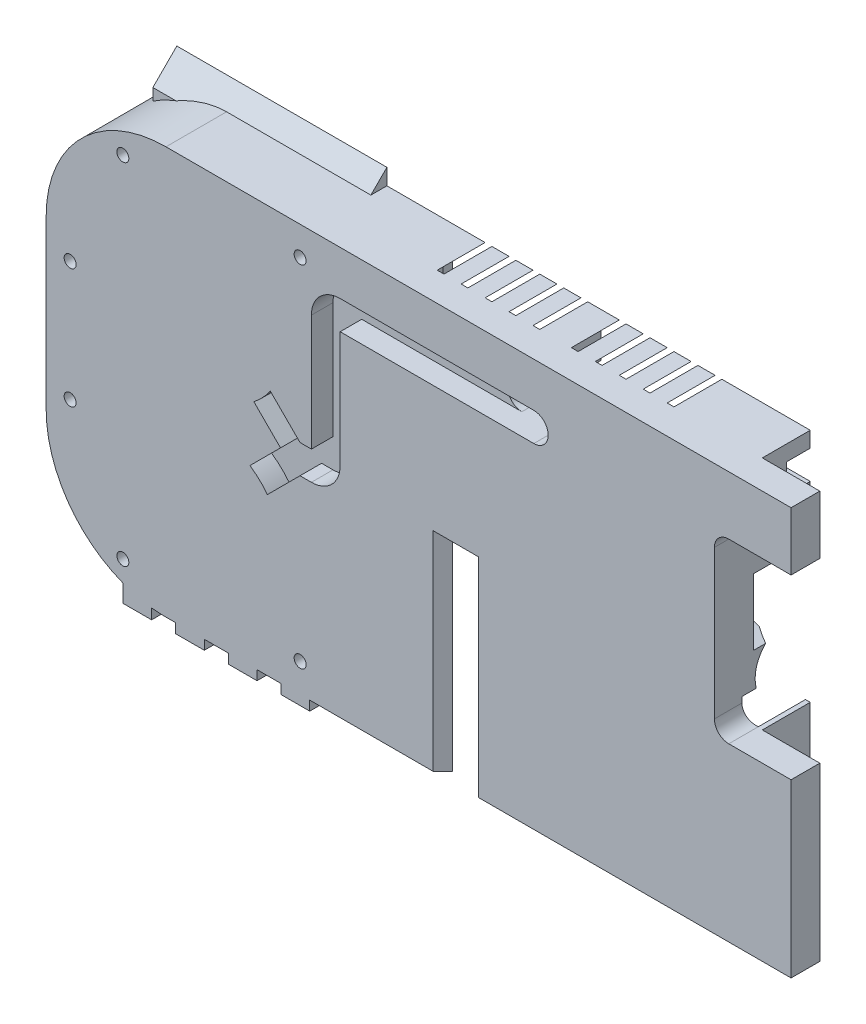
SolidWorks part; units mm, degrees
ref_plane "Front Plane" through (0, 0, 0) normal (0, 0, 1) x (1, 0, 0)
ref_plane "Top Plane" through (0, 0, 0) normal (0, 1, 0) x (1, 0, 0)
ref_plane "Right Plane" through (0, 0, 0) normal (1, 0, 0) x (0, 0, -1)
sketch "mech-front" plane through (0, 0, 0) normal (0, 0, 1) x (1, 0, 0)
  line L0 (-90.64, 57.83) -> (-90.64, 97.83) construction
  line L4 (74.3789, 74.83) -> (74.3789, 82.0953) construction
  line L5 (41.8228, 3) -> (41.8228, 36) construction
  line L6 (-40.1772, 3) -> (-40.1772, 36) construction
  line L7 (-40.64, 97.83) -> (-40.64, 57.83) construction
  line L12 (-85.7883, 97.83) -> (-90.64, 97.83)
  line L13 (-90.64, 97.83) -> (-90.64, 57.83)
  line L14 (-90.64, 57.83) -> (-85.7883, 57.83)
  line L15 (-45.4916, 57.83) -> (-40.64, 57.83)
  line L16 (-40.64, 57.83) -> (-40.64, 97.83)
  line L17 (-40.64, 97.83) -> (-45.4916, 97.83)
  line L20 (39.9162, 72.83) -> (70.9162, 72.83)
  line L21 (74.3789, 74.83) -> (74.3789, 105.83)
  line L22 (70.9162, 107.83) -> (39.9162, 107.83)
  line L23 (37.9162, 105.83) -> (37.9162, 74.83)
  line L26 (-47.1772, 0) -> (-47.1772, 36)
  line L27 (54.8228, 36) -> (54.8228, 0)
  line L28 (54.8228, 36) -> (41.8228, 36)
  line L30 (-40.1772, 36) -> (41.8228, 36)
  line L31 (-40.1772, 36) -> (-47.1772, 36)
  line L34 (-24.2711, 85.48) -> (56.8789, 85.48)
  line L35 (56.8789, 95.18) -> (-24.2711, 95.18)
  line L38 (-30.2119, 75.9) -> (-33.1772, 75.9)
  line L39 (-40.1772, 68.9) -> (-40.1772, 36)
  line L42 (32.71, 75.9) -> (26.935, 75.9)
  line L43 (41.8228, 68.9) -> (41.8228, 36)
  line L46 (22.035, 75.9) -> (22.035, 88.1)
  line L47 (-23.965, 88.1) -> (-23.965, 75.9)
  line L78 (-30.2119, 75.9) -> (26.935, 75.9)
  line L79 (22.035, 88.1) -> (-23.965, 88.1)
  arc A1 (-24.2711, 95.18) -> (-24.2711, 85.48) centre (-24.2711, 90.33) ccw
  arc A7 (41.8228, 68.9) -> (32.71, 75.9) centre (34.8305, 69.2289) ccw
  arc A8 (-24.2711, 95.18) -> (-24.2711, 85.48) centre (-24.2711, 90.33) ccw construction
  arc A12 (70.9162, 72.83) -> (74.3789, 74.83) centre (72.6234, 73.8718) ccw
  arc A13 (74.3789, 105.83) -> (70.9162, 107.83) centre (72.6234, 106.7882) ccw
  arc A14 (39.9162, 107.83) -> (37.9162, 105.83) centre (39.9162, 105.83) ccw
  arc A15 (37.9162, 74.83) -> (39.9162, 72.83) centre (39.9162, 74.83) ccw
  circle A18 centre (78.6862, 90.2827) radius 1.65
  circle A19 centre (28.1462, 90.2827) radius 1.65
  arc A21 (-45.4916, 97.83) -> (-85.7883, 97.83) centre (-65.64, 96.74) ccw
  arc A23 (-85.7883, 57.83) -> (-45.4916, 57.83) centre (-65.64, 58.92) ccw
  arc A28 (-33.1772, 75.9) -> (-40.1772, 68.9) centre (-33.1772, 68.9) ccw
  dimension "D3" = 7
sketch "Sketch2" plane through (0, 0, 0) normal (0, 0, 1) x (1, 0, 0)
  line L0 (-75.6342, 36) -> (-73.6342, 36)
  line L1 (54.8228, 108.83) -> (54.8228, 121)
  line L2 (54.8228, 121) -> (-75.6342, 121)
  line L3 (-100.6342, 96) -> (-100.6342, 61)
  line L4 (54.8228, 36) -> (54.8228, 66.789)
  line L5 (-45.6342, 31.51) -> (-45.6342, 125.2885) construction
  line L6 (54.8228, 66.789) -> (54.8228, 71.83)
  line L7 (-67.6342, 36) -> (-62.6342, 36)
  line L8 (-45.6342, 36) -> (54.8228, 36)
  line L9 (-45.6342, 36) -> (-45.6342, 34)
  line L10 (-45.6342, 34) -> (-51.6342, 34)
  line L11 (-51.6342, 36) -> (-51.6342, 34)
  line L13 (-56.6342, 36) -> (-56.6342, 34)
  line L14 (-56.6342, 34) -> (-62.6342, 34)
  line L15 (-62.6342, 36) -> (-62.6342, 34)
  line L16 (-56.6342, 36) -> (-51.6342, 36)
  line L17 (-67.6342, 36) -> (-67.6342, 34)
  line L18 (-67.6342, 34) -> (-73.6342, 34)
  line L19 (-73.6342, 36) -> (-73.6342, 34)
  line L20 (-40.1772, 36) -> (-47.1772, 36) construction
  line L22 (-78.6342, 36.1807) -> (-78.6342, 34)
  line L23 (-78.6342, 34) -> (-84.6342, 34)
  line L28 (38.8228, 105.83) -> (38.8228, 74.83)
  line L29 (41.8228, 71.83) -> (54.8228, 71.83)
  line L30 (-84.6342, 37.6762) -> (-84.6342, 34)
  line L31 (54.8228, 108.83) -> (41.8228, 108.83)
  arc A0 (-100.6342, 61) -> (-84.6342, 37.6762) centre (-75.6342, 61) ccw
  arc A1 (-75.6342, 121) -> (-100.6342, 96) centre (-75.6342, 96) ccw
  arc A2 (-78.6342, 36.1807) -> (-75.6342, 36) centre (-75.6342, 61) ccw
  arc A3 (38.8228, 105.83) -> (41.8228, 108.83) centre (41.8228, 105.83) cw
  arc A4 (41.8228, 71.83) -> (38.8228, 74.83) centre (41.8228, 74.83) cw
  point P10 (-100.6342, 36)
  point P13 (-100.6342, 121)
  dimension "D3" = 25
  dimension "D4" = 25
  dimension "D17" = 3
  dimension "D18" = 3
  dimension "D2" = 85
  dimension "D5" = 55
  dimension "D6" = 5
  dimension "D7" = 5
  dimension "D8" = 5
  dimension "D9" = 6
  dimension "D10" = 6
  dimension "D11" = 6
  dimension "D12" = 6
  dimension "D13" = 2
  dimension "D14" = 12.17
  dimension "D15" = 37
  dimension "D16" = 16
  dimension "D19" = 155.457
extrude "body" add sketch "Sketch2" against normal blind 16
sketch "Sketch24" plane through (0, 0, -16) normal (0, 0, -1) x (-1, 0, 0)
  line L0 (-41.8228, 108.83) -> (-54.8228, 108.83) construction
  line L1 (-54.8228, 121) -> (-42.8228, 121)
  line L2 (-54.8228, 121) -> (-54.8228, 108.83)
  line L3 (-54.8228, 108.83) -> (-42.8228, 108.83)
  line L4 (-42.8228, 121) -> (-42.8228, 108.83)
  line L5 (75.6342, 36) -> (73.6342, 36) construction
  line L6 (-54.8228, 71.83) -> (-42.8228, 71.83)
  line L7 (-54.8228, 71.83) -> (-54.8228, 36)
  line L8 (-54.8228, 36) -> (-42.8228, 36)
  line L9 (-42.8228, 71.83) -> (-42.8228, 36)
  dimension "D1" = 12
  dimension "D2" = 12
extrude "handle mate" cut sketch "Sketch24" against normal blind 10
sketch "Sketch17" plane through (0, 0, -16) normal (0, 0, -1) x (-1, 0, 0)
  line L0 (-42.8228, 121) -> (75.6342, 121) construction
  line L1 (45.5249, 121) -> (75.6342, 121)
  line L2 (45.5249, 121) -> (45.5249, 125.3507)
  line L3 (45.5249, 125.3507) -> (89.3694, 125.3507)
  line L4 (89.3694, 121) -> (89.3694, 125.3507)
  line L5 (89.3694, 121) -> (89.3694, 116.8889)
  arc A0 (100.6342, 96) -> (75.6342, 121) centre (75.6342, 96) ccw construction
  arc A1 (89.3694, 116.8889) -> (75.6342, 121) centre (75.6342, 96) ccw
extrude "aim" add sketch "Sketch17" against normal blind 5
chamfer "aim chamf" distance 6 angle 45 1 edges at (-67.4471, 125.3507, -11)
sketch "Sketch4" plane through (0, 36, 0) normal (0, -1, 0) x (1, 0, 0)
  line L0 (-40.1772, -16) -> (-40.1772, -6.393)
  line L1 (41.8228, -6.8) -> (41.8228, -25.2) construction
  line L3 (-40.1772, -6.393) -> (-30.1772, -4.8597)
  line L4 (-30.1772, -4.8597) -> (-30.1772, -5.2667)
  line L5 (-30.1772, -5.2667) -> (-28.6772, -5.0367)
  line L6 (-28.6772, -5.0367) -> (-28.6772, -4.6297)
  line L7 (-28.6772, -4.6297) -> (-25.1772, -4.093)
  line L8 (-25.1772, -4.093) -> (-25.1772, -2)
  line L9 (-25.1772, -2) -> (-11.7772, -2)
  line L10 (-11.7772, -2) -> (-11.7772, -3)
  line L11 (-11.7772, -3) -> (-10.1772, -3)
  line L12 (-10.1772, -3) -> (-10.1772, -2)
  line L13 (-10.1772, -2) -> (11.8228, -2)
  line L14 (11.8228, -2) -> (11.8228, -3)
  line L15 (11.8228, -3) -> (13.4228, -3)
  line L16 (13.4228, -3) -> (13.4228, -2)
  line L17 (13.4228, -2) -> (24.32, -2)
  line L18 (24.32, -2) -> (24.32, -6.5)
  line L19 (24.32, -6.5) -> (28.82, -6.5)
  line L20 (28.82, -6.5) -> (28.82, -4.1992)
  line L21 (28.82, -4.1992) -> (30.2228, -4.4143)
  line L22 (30.2228, -4.4143) -> (30.2228, -5.0213)
  line L23 (30.2228, -5.0213) -> (31.8228, -5.2667)
  line L24 (31.8228, -5.2667) -> (31.8228, -4.6597)
  line L25 (31.8228, -4.6597) -> (41.8228, -6.193)
  line L26 (41.8228, -6.193) -> (41.8228, -16)
  line L28 (-75.6342, -16) -> (-73.6342, -16) construction
  line L29 (-40.1772, -16) -> (41.8228, -16)
extrude "clip body clearance" cut sketch "Sketch4" against normal blind 40
sketch "Sketch5" plane through (0, 76, 0) normal (0, -1, 0) x (1, 0, 0)
  line L9 (-11.7772, -2) -> (-25.1772, -2) construction
  line L10 (-11.7772, -3) -> (-11.7772, -2) construction
  line L11 (-10.1772, -3) -> (-11.7772, -3) construction
  line L12 (-10.1772, -2) -> (-10.1772, -3) construction
  line L13 (11.8228, -2) -> (-10.1772, -2) construction
  line L14 (11.8228, -3) -> (11.8228, -2) construction
  line L15 (13.4228, -2) -> (13.4228, -3) construction
  line L16 (13.4228, -3) -> (11.8228, -3) construction
  line L17 (24.32, -2) -> (13.4228, -2) construction
  line L18 (-11.7772, -2) -> (-25.1772, -2)
  line L19 (-11.7772, -3) -> (-11.7772, -2)
  line L21 (-10.1772, -3) -> (-11.7772, -3)
  line L22 (-10.1772, -2) -> (-10.1772, -3)
  line L23 (11.8228, -2) -> (-10.1772, -2)
  line L24 (11.8228, -3) -> (11.8228, -2)
  line L25 (13.4228, -2) -> (13.4228, -3)
  line L26 (13.4228, -3) -> (11.8228, -3)
  line L27 (24.32, -2) -> (13.4228, -2)
  line L28 (-25.1772, -2) -> (-25.1772, -16)
  line L29 (-40.1772, -16) -> (38.8228, -16) construction
  line L30 (24.32, -2) -> (24.32, -16)
  line L31 (24.32, -16) -> (-25.1772, -16)
extrude "clip head clearance" cut sketch "Sketch5" against normal blind 13
sketch "Sketch30" plane through (0, 0, 0) normal (0, 0, 1) x (1, 0, 0)
  line L1 (-45.6342, 36) -> (54.8228, 36) construction
  line L2 (-12.3772, 36) -> (-17.8772, 36)
  line L3 (-12.3772, 36) -> (-12.3772, 77.5)
  line L4 (-12.3772, 77.5) -> (-17.8772, 77.5)
  line L8 (-17.8772, 36) -> (-17.8772, 77.5)
  line L9 (-12.3772, 19.5) -> (-12.3772, 36) construction
  line L10 (-17.8772, 19.5) -> (-12.3772, 19.5) construction
  line L11 (-17.8772, 36) -> (-17.8772, 19.5) construction
  point P8 (-15.1272, 19.5)
  dimension "D1" = 58
extrude "clip window" cut sketch "Sketch30" against normal up to next
chamfer "clip window chamf" distance 2 angle 45 3 edges at (-17.8772, 56.75, 0) (-15.1272, 77.5, 0) (-12.3772, 56.75, 0)
hole_wizard "clip screw M3" positions "Sketch21" profile "Sketch20" tap size "M3" standard "DIN"
sketch "Sketch21" plane through (0, 36, 0) normal (0, -1, 0) x (-1, 0, 0)
  point P0 (-51.8228, 3)
  point P2 (42.1772, 3)
sketch "Sketch20" plane through (51.8228, 36, -3) normal (1, 0, 0) x (0, 0, -1)
  line L0 (0, 0) -> (0, 16.7511)
  line L1 (0, 16.7511) -> (1.25, 16)
  line L2 (1.25, 16) -> (1.25, 0)
  line L5 (1.25, 0) -> (0, 0)
  line L10 (0, 16.7511) -> (-1.25, 16) construction
  line L11 (0, -6.35) -> (0, 107.95) construction
  dimension "Tap Drill Dia." = 2.5
  dimension "Tap Drill Depth" = 16
  dimension "Drill Angle" = 118
cosmetic thread "Hole Thread11" parameters "D1"=16, "D2"=3
cosmetic thread "Hole Thread29" parameters "D1"=16, "D2"=3
sketch "Sketch6" plane through (-100.6342, 0, 0) normal (-1, 0, 0) x (0, 0, 1)
  line L0 (-16, 96) -> (-16, 61) construction
  line L1 (-6.393, 36) -> (-16, 36) construction
  circle A0 centre (-16, 77.83) radius 7.5
  point P4 (-11.1965, 36)
  dimension "D1" = 41.83
extrude "dart clearance" cut sketch "Sketch6" against normal up to surface (139.457 mm away) up to face at (38.8228, 85.5533, -7.2443)
sketch "Sketch15" plane through (0, 0, -16) normal (0, 0, -1) x (-1, 0, 0)
  line L0 (100.6342, 77.83) -> (-54.8228, 77.83) construction
  line L1 (100.6342, 70.33) -> (100.6342, 85.33) construction
  line L2 (-54.8228, 36) -> (-54.8228, 71.83) construction
  circle A0 centre (24.2711, 90.33) radius 6.85
  arc A1 (24.2711, 85.48) -> (24.2711, 95.18) centre (24.2711, 90.33) ccw construction
extrude "drive pulley clearance" cut sketch "Sketch15" against normal blind 5.5
sketch "Sketch7" plane through (0, 0, -16) normal (0, 0, -1) x (-1, 0, 0)
  line L0 (-38.8228, 85.33) -> (-38.8228, 105.83) construction
  line L2 (-38.8228, 97.18) -> (-38.8228, 83.48)
  line L6 (27.64, 83.48) -> (-38.8228, 83.48)
  line L7 (-38.8228, 97.18) -> (27.64, 97.18)
  arc A0 (28.9532, 85.33) -> (17.5514, 89) centre (24.2711, 90.33) ccw construction
  arc A3 (27.64, 83.48) -> (27.64, 97.18) centre (24.2711, 90.33) ccw
sketch "Sketch16" plane through (0, 0, -16) normal (0, 0, -1) x (-1, 0, 0)
  circle A0 centre (24.2711, 90.33) radius 4.995
  arc A1 (28.9532, 85.33) -> (17.5514, 89) centre (24.2711, 90.33) ccw construction
  dimension "D1" = 9.99
extrude "drive bearing clearance" cut sketch "Sketch16" against normal blind 14
sketch "Sketch12" plane through (0, 0, 0) normal (0, 0, 1) x (1, 0, 0)
  line L1 (-67.1027, 96.74) -> (-48.1927, 77.83) construction
  line L2 (-54.4635, 68.7308) -> (-47.6572, 75.5371)
  line L3 (-57.292, 84.1008) -> (-51.7283, 78.5371)
  line L4 (-58.111, 72.1544) -> (-51.7283, 78.5371)
  line L5 (-53.8683, 87.7483) -> (-47.6572, 81.5371)
  line L7 (-68.5169, 95.3258) -> (-41.5922, 68.4011) construction
  line L8 (-64.9814, 98.8613) -> (-38.0567, 71.9366) construction
  line L9 (-42.2824, 81.5371) -> (-42.2824, 105.7547) construction
  line L11 (-51.7283, 78.5371) -> (-45.2824, 78.5371) construction
  line L13 (-39.2824, 108.7547) -> (1.1362, 108.7547) construction
  line L15 (-39.2824, 81.5371) -> (-39.2824, 105.7547)
  line L16 (-39.2824, 105.7547) -> (1.1362, 105.7547)
  line L17 (-47.6572, 75.5371) -> (-45.2824, 75.5371)
  line L18 (-45.2824, 81.5371) -> (-45.2824, 105.7547)
  line L19 (-39.2824, 111.7547) -> (1.1362, 111.7547)
  line L20 (-47.7785, 78.2442) -> (-30.5987, 95.4241) construction
  line L21 (-47.6572, 81.5371) -> (-45.2824, 81.5371)
  line L22 (-67.1027, 96.74) -> (-40.178, 69.8153) construction
  line L25 (-51.7283, 81.5371) -> (-45.2824, 81.5371) construction
  line L26 (-51.7283, 75.5371) -> (-45.2824, 75.5371) construction
  arc A1 (-54.4635, 68.7308) -> (-58.111, 72.1544) centre (-67.1027, 58.92) ccw
  arc A3 (-57.292, 84.1008) -> (-53.8683, 87.7483) centre (-67.1027, 96.74) ccw
  arc A4 (-42.2824, 105.7547) -> (-39.2824, 108.7547) centre (-39.2824, 105.7547) cw construction
  arc A5 (-42.2824, 81.5371) -> (-45.2824, 78.5371) centre (-45.2824, 81.5371) cw construction
  arc A6 (-39.2824, 81.5371) -> (-45.2824, 75.5371) centre (-45.2824, 81.5371) cw
  arc A7 (-39.2824, 105.7547) -> (-39.2824, 105.7547) centre (-39.2824, 105.7547) cw
  arc A8 (-45.2824, 81.5371) -> (-45.2824, 81.5371) centre (-45.2824, 81.5371) cw
  arc A9 (-45.2824, 105.7547) -> (-39.2824, 111.7547) centre (-39.2824, 105.7547) cw
  arc A10 (1.1362, 111.7547) -> (1.1362, 105.7547) centre (1.1362, 108.7547) cw
  point P6 (-65.6885, 57.5058)
  point P7 (-29.1844, 94.0099)
  point P10 (-69.224, 61.0413)
  point P11 (-32.72, 97.5454)
  dimension "D4" = 3
  dimension "D7" = 135
  dimension "D1" = 2
  dimension "D2" = 3
  dimension "D5" = 3
  dimension "D6" = 3
extrude "ESC_wire guide" cut sketch "Sketch12" against normal blind 4.5
sketch "Sketch13" plane through (0, 0, -4.5) normal (0, 0, 1) x (1, 0, 0)
  line L0 (1.1362, 108.7547) -> (-5.8638, 108.7547) construction
  line L1 (1.1362, 105.7547) -> (-5.8638, 105.7547)
  line L2 (1.1362, 111.7547) -> (-5.8638, 111.7547)
  line L3 (1.1362, 111.7547) -> (-39.2824, 111.7547) construction
  arc A0 (1.1362, 105.7547) -> (1.1362, 111.7547) centre (1.1362, 108.7547) ccw
  arc A1 (-5.8638, 111.7547) -> (-5.8638, 105.7547) centre (-5.8638, 108.7547) ccw
  point P3 (-2.3638, 108.7547)
  dimension "D1" = 7
extrude "ESC_wire feedtrough" cut sketch "Sketch13" against normal up to next
sketch "Sketch14" plane through (0, 0, -16) normal (0, 0, -1) x (-1, 0, 0)
  line L0 (5.8638, 111.7547) -> (-1.1362, 111.7547) construction
  line L1 (-24.1362, 117.7547) -> (-21.1362, 117.7547)
  line L2 (-24.1362, 117.7547) -> (-24.1362, 111.7547)
  line L3 (-24.1362, 111.7547) -> (-4.1362, 111.7547)
  line L4 (0.8638, 117.7547) -> (0.8638, 111.0476)
  line L5 (8.8638, 111.7547) -> (28.8638, 111.7547)
  line L6 (3.8638, 111.0476) -> (3.8638, 117.7547)
  line L7 (3.8638, 117.7547) -> (6.8638, 117.7547)
  line L8 (28.8638, 111.7547) -> (28.8638, 117.7547)
  line L9 (-22.9673, 121) -> (-19.722, 117.7547)
  line L10 (-24.3815, 121) -> (-21.1362, 117.7547)
  line L11 (-42.8228, 121) -> (45.5249, 121) construction
  line L12 (0.8638, 111.0476) -> (0.8638, 108.7547)
  line L13 (0.8638, 108.7547) -> (-4.1362, 108.7547)
  line L14 (-4.1362, 111.7547) -> (-4.1362, 108.7547)
  line L15 (-19.3815, 121) -> (-16.1362, 117.7547)
  line L16 (3.8638, 111.0476) -> (3.8638, 108.7547)
  line L17 (3.8638, 108.7547) -> (8.8638, 108.7547)
  line L18 (8.8638, 111.7547) -> (8.8638, 108.7547)
  line L19 (-17.9673, 121) -> (-14.722, 117.7547)
  line L20 (-14.3815, 121) -> (-11.1362, 117.7547)
  line L21 (-12.9673, 121) -> (-9.722, 117.7547)
  line L22 (-9.3815, 121) -> (-6.1362, 117.7547)
  line L23 (-7.9673, 121) -> (-4.722, 117.7547)
  line L24 (-4.3815, 121) -> (-1.1362, 117.7547)
  line L25 (-2.9673, 121) -> (0.278, 117.7547)
  line L26 (3.6185, 121) -> (6.8638, 117.7547)
  line L27 (5.0327, 121) -> (8.278, 117.7547)
  line L28 (8.6185, 121) -> (11.8638, 117.7547)
  line L29 (10.0327, 121) -> (13.278, 117.7547)
  line L30 (13.6185, 121) -> (16.8638, 117.7547)
  line L31 (15.0327, 121) -> (18.278, 117.7547)
  line L32 (18.6185, 121) -> (21.8638, 117.7547)
  line L33 (20.0327, 121) -> (23.278, 117.7547)
  line L34 (23.6185, 121) -> (26.8638, 117.7547)
  line L35 (25.0327, 121) -> (28.278, 117.7547)
  line L36 (-24.3815, 121) -> (-22.9673, 121)
  line L37 (-19.3815, 121) -> (-17.9673, 121)
  line L38 (-14.3815, 121) -> (-12.9673, 121)
  line L39 (-9.3815, 121) -> (-7.9673, 121)
  line L40 (-4.3815, 121) -> (-2.9673, 121)
  line L41 (3.6185, 121) -> (5.0327, 121)
  line L42 (8.6185, 121) -> (10.0327, 121)
  line L43 (13.6185, 121) -> (15.0327, 121)
  line L44 (18.6185, 121) -> (20.0327, 121)
  line L45 (23.6185, 121) -> (25.0327, 121)
  line L46 (-14.722, 117.7547) -> (-11.1362, 117.7547)
  line L47 (-19.722, 117.7547) -> (-16.1362, 117.7547)
  line L48 (-9.722, 117.7547) -> (-6.1362, 117.7547)
  line L49 (-4.722, 117.7547) -> (-1.1362, 117.7547)
  line L50 (0.278, 117.7547) -> (0.8638, 117.7547)
  line L51 (8.278, 117.7547) -> (11.8638, 117.7547)
  line L52 (13.278, 117.7547) -> (16.8638, 117.7547)
  line L53 (18.278, 117.7547) -> (21.8638, 117.7547)
  line L54 (23.278, 117.7547) -> (26.8638, 117.7547)
  line L55 (28.278, 117.7547) -> (28.8638, 117.7547)
  arc A0 (-1.1362, 111.7547) -> (-1.1362, 105.7547) centre (-1.1362, 108.7547) ccw construction
  arc A1 (5.8638, 105.7547) -> (5.8638, 111.7547) centre (5.8638, 108.7547) ccw construction
  dimension "D1" = 3
  dimension "D2" = 25
  dimension "D3" = 25
  dimension "D4" = 5
  dimension "D5" = 6
  dimension "D6" = 6
  dimension "D7" = 1
  dimension "D9" = 3
  dimension "D10" = 135
  dimension "D11" = 1
  dimension "D12" = 3
  dimension "D13" = 135
  dimension "D8" = 5
  dimension "D14" = 5
extrude "ESC clearance" cut sketch "Sketch14" against normal blind 10
sketch "Sketch27" plane through (0, 0, -16) normal (0, 0, -1) x (-1, 0, 0)
  line L0 (-42.8228, 108.83) -> (-42.8228, 121) construction
  line L1 (-27.2593, 111.7547) -> (-42.8228, 111.7547)
  line L2 (-24.1362, 111.7547) -> (-24.1362, 117.7547)
  line L3 (-24.1362, 117.7547) -> (-42.8228, 117.7547)
  line L4 (-42.8228, 111.7547) -> (-42.8228, 117.7547)
  line L6 (-24.1362, 111.7547) -> (28.8638, 111.7547)
  line L8 (-24.1362, 108.7547) -> (31.8638, 108.7547)
  line L9 (31.8638, 111.7044) -> (31.8638, 108.7547)
  line L10 (28.8638, 117.7547) -> (31.8638, 117.7547)
  line L11 (28.8638, 117.7547) -> (28.8638, 111.7547)
  line L13 (31.8638, 117.7547) -> (31.8638, 111.7044)
  line L16 (-24.1362, 108.7547) -> (-27.2593, 108.7547)
  line L17 (-27.2593, 111.7547) -> (-27.2593, 108.7547)
  dimension "D1" = 3
  dimension "D2" = 3
extrude "ESC wire clearance" cut sketch "Sketch27" against normal blind 5
hole_wizard "body screw M3" positions "Sketch19" profile "Sketch18" tap size "M3" standard "DIN" end condition through all
sketch "Sketch19" plane through (0, 0, -16) normal (0, 0, -1) x (-1, 0, 0)
  line L2 (100.6342, 96) -> (100.6342, 85.33) construction
  line L5 (100.6342, 70.33) -> (100.6342, 61) construction
  line L7 (75.6342, 36) -> (73.6342, 36) construction
  line L8 (100.6342, 70.33) -> (100.6342, 85.33) construction
  point P0 (47.6342, 42)
  point P2 (84.6342, 42)
  point P4 (84.6342, 115)
  point P6 (47.6342, 115)
  point P14 (95.6342, 90.33)
  point P16 (95.6342, 65.33)
  point P24 (100.6342, 90.665)
  point P57 (100.6342, 77.83)
  dimension "D2" = 16
  dimension "D3" = 37
  dimension "D7" = 5
  dimension "D8" = 25
  dimension "D9" = 6
  dimension "D10" = 12.5
cosmetic thread "Hole Thread1" parameters "D2"=3
cosmetic thread "Hole Thread2" parameters "D2"=3
cosmetic thread "Hole Thread6" parameters "D2"=3
cosmetic thread "Hole Thread7" parameters "D2"=3
cosmetic thread "Hole Thread8" parameters "D2"=3
cosmetic thread "Hole Thread9" parameters "D2"=3
sketch "Sketch18" plane through (-47.6342, 42, -16) normal (1, 0, 0) x (0, 1, 0)
  line L0 (0, 0) -> (0, 16)
  line L1 (0, 16) -> (1.25, 16)
  line L2 (1.25, 16) -> (1.25, 0)
  line L5 (1.25, 0) -> (0, 0)
  line L11 (0, -6.35) -> (0, 107.95) construction
  dimension "Thru Tap Drill Dia." = 2.5
  dimension "Thru Tap Drill Depth" = 16
sketch "Sketch31" plane through (0, 0, -16) normal (0, 0, -1) x (-1, 0, 0)
  line L1 (100.6342, 85.33) -> (93.1342, 85.33)
  line L2 (100.6342, 85.33) -> (100.6342, 87.33)
  line L3 (100.6342, 87.33) -> (98.1342, 87.33)
  line L4 (91.14, 77.83) -> (100.6342, 77.83) construction
  line L6 (93.1342, 87.33) -> (93.1342, 85.33)
  line L7 (93.1342, 87.33) -> (93.1342, 92.83)
  line L8 (93.1342, 92.83) -> (98.1342, 92.83)
  line L9 (98.1342, 87.33) -> (98.1342, 92.83)
  line L11 (100.6342, 70.33) -> (100.6342, 85.33) construction
  circle A1 centre (95.6342, 90.33) radius 1.25 construction
  dimension "D3" = 2.5
  dimension "D1" = 5
  dimension "D2" = 2.5
  dimension "D4" = 2
revolve "barrel connector" cut sketch "Sketch31" angle 360 about L4
extrude "Cut-Extrude1" cut sketch "Sketch7" against normal blind 4
hole_wizard "drive motor screw" positions "Sketch34" profile "Sketch33" tap size "M3" standard "DIN"
sketch "Sketch34" plane through (0, 0, -12) normal (0, 0, -1) x (-1, 0, 0)
  circle A1 centre (-28.1462, 90.2827) radius 1.65 construction
  point P0 (-28.1462, 90.2827)
sketch "Sketch33" plane through (28.1462, 90.2827, -12) normal (1, 0, 0) x (0, 1, 0)
  line L0 (0, 0) -> (0, 11.7511)
  line L1 (0, 11.7511) -> (1.25, 11)
  line L2 (1.25, 11) -> (1.25, 0)
  line L5 (1.25, 0) -> (0, 0)
  line L10 (0, 11.7511) -> (-1.25, 11) construction
  line L11 (0, -6.35) -> (0, 107.95) construction
  dimension "Tap Drill Dia." = 2.5
  dimension "Tap Drill Depth" = 11
  dimension "Drill Angle" = 118
cosmetic thread "Hole Thread22" parameters "D1"=9.5, "D2"=3
sketch "Sketch36" plane through (0, 0, -12) normal (0, 0, -1) x (-1, 0, 0)
  line L2 (-38.8228, 96.9834) -> (-38.8228, 83.1322)
  line L4 (-37.9375, 83.4874) -> (-30.1381, 86.6168)
  line L5 (-30.3076, 94.0122) -> (-37.8731, 96.652)
  line L6 (-38.8228, 83.1322) -> (-30.1381, 86.6168)
  line L7 (-30.3076, 94.0122) -> (-38.8228, 96.9834)
  line L11 (-38.8228, 97.18) -> (-38.8228, 105.83) construction
  arc A2 (-30.1381, 86.6168) -> (-30.3076, 94.0122) centre (-31.6089, 90.2827) ccw
  arc A3 (-30.1381, 86.6168) -> (-30.3076, 94.0122) centre (-31.6089, 90.2827) ccw
  dimension "D1" = 0.5
extrude "drive motor ear" cut sketch "Sketch36" against normal blind 3.8
